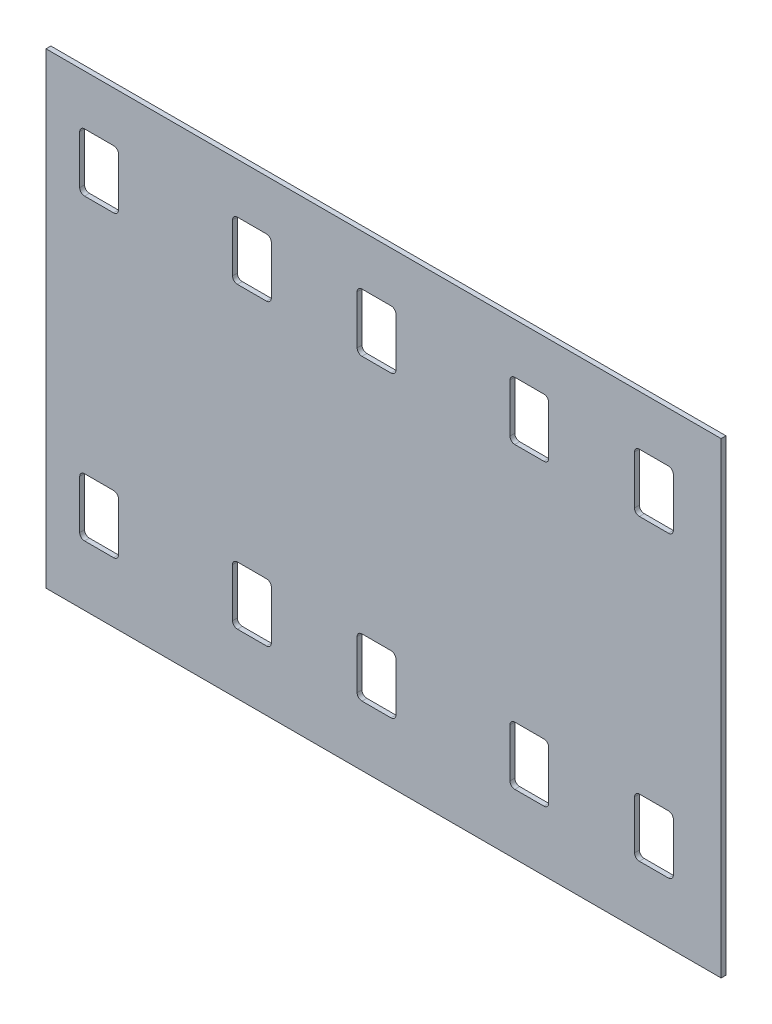
SolidWorks part; units mm, degrees
material "PP Film"
ref_plane "X-Y Datum" through (0, 0, 0) normal (0, 0, 1) x (1, 0, 0)
ref_plane "X-Z Datum" through (0, 0, 0) normal (0, 1, 0) x (1, 0, 0)
ref_plane "Y-Z Datum" through (0, 0, 0) normal (1, 0, 0) x (0, 0, -1)
sketch "Sketch1" plane through (0, 0, 0) normal (0, 0, 1) x (1, 0, 0)
  line L48 (-220.9897, 149.5877) -> (-220.9897, -156.2291)
  line L49 (-220.9897, -156.2291) -> (220.9897, -156.2291)
  line L50 (220.9897, -156.2291) -> (220.9897, 149.5877)
  line L51 (220.9897, 149.5877) -> (-220.9897, 149.5877)
extrude "Boss-Extrude1" add sketch "Sketch1" along normal blind 3.175 contours L50 L51 L48 L49 region at (0, -3.3207, 0)
sketch "Sketch2" plane through (0, 0, 3.175) normal (0, 0, 1) x (1, 0, 0)
  line L0 (-195.7605, 116.8) -> (-176.7105, 116.8) construction
  line L1 (-198.9355, 113.625) -> (-198.9355, 81.875) construction
  line L2 (-195.7605, 78.7) -> (-176.7105, 78.7) construction
  line L3 (-173.5355, 113.625) -> (-173.5355, 81.875) construction
  line L8 (-195.7605, 116.8) -> (-176.7105, 116.8)
  line L9 (-198.9355, 113.625) -> (-198.9355, 81.875)
  line L10 (-195.7605, 78.7) -> (-176.7105, 78.7)
  line L11 (-173.5355, 113.625) -> (-173.5355, 81.875)
  line L16 (-195.7605, -78.7) -> (-176.7105, -78.7) construction
  line L17 (-173.5355, -81.875) -> (-173.5355, -113.625) construction
  line L18 (-198.9355, -81.875) -> (-198.9355, -113.625) construction
  line L19 (-195.7605, -116.8) -> (-176.7105, -116.8) construction
  line L24 (-195.7605, -78.7) -> (-176.7105, -78.7)
  line L25 (-173.5355, -81.875) -> (-173.5355, -113.625)
  line L26 (-198.9355, -81.875) -> (-198.9355, -113.625)
  line L27 (-195.7605, -116.8) -> (-176.7105, -116.8)
  line L32 (-76.6655, -78.7) -> (-95.7155, -78.7) construction
  line L33 (-98.8905, -81.875) -> (-98.8905, -113.625) construction
  line L34 (-73.4905, -113.625) -> (-73.4905, -81.875) construction
  line L35 (-95.7155, -116.8) -> (-76.6655, -116.8) construction
  line L36 (-76.6655, -78.7) -> (-95.7155, -78.7)
  line L37 (-98.8905, -81.875) -> (-98.8905, -113.625)
  line L38 (-73.4905, -113.625) -> (-73.4905, -81.875)
  line L39 (-95.7155, -116.8) -> (-76.6655, -116.8)
  line L40 (-76.6655, 116.8) -> (-95.7155, 116.8) construction
  line L41 (-73.4905, 81.875) -> (-73.4905, 113.625) construction
  line L42 (-98.8905, 113.625) -> (-98.8905, 81.875) construction
  line L43 (-95.7155, 78.7) -> (-76.6655, 78.7) construction
  line L44 (-76.6655, 116.8) -> (-95.7155, 116.8)
  line L45 (-73.4905, 81.875) -> (-73.4905, 113.625)
  line L46 (-98.8905, 113.625) -> (-98.8905, 81.875)
  line L47 (-95.7155, 78.7) -> (-76.6655, 78.7)
  arc A0 (-173.5355, 113.625) -> (-176.7105, 116.8) centre (-176.7105, 113.625) ccw construction
  arc A1 (-195.7605, 116.8) -> (-198.9355, 113.625) centre (-195.7605, 113.625) ccw construction
  arc A2 (-198.9355, 81.875) -> (-195.7605, 78.7) centre (-195.7605, 81.875) ccw construction
  arc A3 (-176.7105, 78.7) -> (-173.5355, 81.875) centre (-176.7105, 81.875) ccw construction
  arc A8 (-173.5355, 113.625) -> (-176.7105, 116.8) centre (-176.7105, 113.625) ccw
  arc A9 (-195.7605, 116.8) -> (-198.9355, 113.625) centre (-195.7605, 113.625) ccw
  arc A10 (-198.9355, 81.875) -> (-195.7605, 78.7) centre (-195.7605, 81.875) ccw
  arc A11 (-176.7105, 78.7) -> (-173.5355, 81.875) centre (-176.7105, 81.875) ccw
  arc A16 (-195.7605, -78.7) -> (-198.9355, -81.875) centre (-195.7605, -81.875) ccw construction
  arc A17 (-173.5355, -81.875) -> (-176.7105, -78.7) centre (-176.7105, -81.875) ccw construction
  arc A18 (-176.7105, -116.8) -> (-173.5355, -113.625) centre (-176.7105, -113.625) ccw construction
  arc A19 (-198.9355, -113.625) -> (-195.7605, -116.8) centre (-195.7605, -113.625) ccw construction
  arc A24 (-195.7605, -78.7) -> (-198.9355, -81.875) centre (-195.7605, -81.875) ccw
  arc A25 (-173.5355, -81.875) -> (-176.7105, -78.7) centre (-176.7105, -81.875) ccw
  arc A26 (-176.7105, -116.8) -> (-173.5355, -113.625) centre (-176.7105, -113.625) ccw
  arc A27 (-198.9355, -113.625) -> (-195.7605, -116.8) centre (-195.7605, -113.625) ccw
  arc A32 (-73.4905, -81.875) -> (-76.6655, -78.7) centre (-76.6655, -81.875) ccw construction
  arc A33 (-95.7155, -78.7) -> (-98.8905, -81.875) centre (-95.7155, -81.875) ccw construction
  arc A34 (-76.6655, -116.8) -> (-73.4905, -113.625) centre (-76.6655, -113.625) ccw construction
  arc A35 (-98.8905, -113.625) -> (-95.7155, -116.8) centre (-95.7155, -113.625) ccw construction
  arc A36 (-73.4905, -81.875) -> (-76.6655, -78.7) centre (-76.6655, -81.875) ccw
  arc A37 (-95.7155, -78.7) -> (-98.8905, -81.875) centre (-95.7155, -81.875) ccw
  arc A38 (-76.6655, -116.8) -> (-73.4905, -113.625) centre (-76.6655, -113.625) ccw
  arc A39 (-98.8905, -113.625) -> (-95.7155, -116.8) centre (-95.7155, -113.625) ccw
  arc A40 (-73.4905, 113.625) -> (-76.6655, 116.8) centre (-76.6655, 113.625) ccw construction
  arc A41 (-95.7155, 116.8) -> (-98.8905, 113.625) centre (-95.7155, 113.625) ccw construction
  arc A42 (-76.6655, 78.7) -> (-73.4905, 81.875) centre (-76.6655, 81.875) ccw construction
  arc A43 (-98.8905, 81.875) -> (-95.7155, 78.7) centre (-95.7155, 81.875) ccw construction
  arc A44 (-73.4905, 113.625) -> (-76.6655, 116.8) centre (-76.6655, 113.625) ccw
  arc A45 (-95.7155, 116.8) -> (-98.8905, 113.625) centre (-95.7155, 113.625) ccw
  arc A46 (-76.6655, 78.7) -> (-73.4905, 81.875) centre (-76.6655, 81.875) ccw
  arc A47 (-98.8905, 81.875) -> (-95.7155, 78.7) centre (-95.7155, 81.875) ccw
extrude "Cut-Extrude1" cut sketch "Sketch2" against normal through all contours L26 A27 L27 A26 L25 A25 L24 A24 | L10 A11 L11 A8 L8 A9 L9 A10 region at (-186.2355, 97.75, 3.175) region at (-186.2355, -97.75, 3.175)
sketch "Sketch3" plane through (0, 0, 3.175) normal (0, 0, 1) x (1, 0, 0)
  line L5 (-176.7105, 116.8) -> (-195.7605, 116.8)
  line L6 (-173.5355, 81.875) -> (-173.5355, 113.625)
  line L7 (-195.7605, 78.7) -> (-176.7105, 78.7)
  line L13 (-198.9355, 113.625) -> (-198.9355, 81.875)
  line L14 (-176.7105, 116.8) -> (-195.7605, 116.8)
  line L15 (-173.5355, 81.875) -> (-173.5355, 113.625)
  line L21 (-195.7605, 78.7) -> (-176.7105, 78.7)
  line L22 (-198.9355, 113.625) -> (-198.9355, 81.875)
  line L23 (-173.5355, -113.625) -> (-173.5355, -81.875)
  line L29 (-195.7605, -116.8) -> (-176.7105, -116.8)
  line L30 (-198.9355, -81.875) -> (-198.9355, -113.625)
  line L31 (-176.7105, -78.7) -> (-195.7605, -78.7)
  line L36 (-173.5355, -113.625) -> (-173.5355, -81.875)
  line L37 (-195.7605, -116.8) -> (-176.7105, -116.8)
  line L38 (-198.9355, -81.875) -> (-198.9355, -113.625)
  line L39 (-176.7105, -78.7) -> (-195.7605, -78.7)
  line L40 (-76.6655, 116.8) -> (-95.7155, 116.8)
  line L41 (-98.8905, 113.625) -> (-98.8905, 81.875)
  line L42 (-95.7155, 78.7) -> (-76.6655, 78.7)
  line L43 (-73.4905, 81.875) -> (-73.4905, 113.625)
  line L44 (-76.6655, 116.8) -> (-95.7155, 116.8)
  line L45 (-98.8905, 113.625) -> (-98.8905, 81.875)
  line L46 (-95.7155, 78.7) -> (-76.6655, 78.7)
  line L47 (-73.4905, 81.875) -> (-73.4905, 113.625)
  line L48 (-95.7155, -116.8) -> (-76.6655, -116.8)
  line L49 (-98.8905, -81.875) -> (-98.8905, -113.625)
  line L50 (-76.6655, -78.7) -> (-95.7155, -78.7)
  line L51 (-73.4905, -113.625) -> (-73.4905, -81.875)
  line L52 (-95.7155, -116.8) -> (-76.6655, -116.8)
  line L53 (-98.8905, -81.875) -> (-98.8905, -113.625)
  line L54 (-76.6655, -78.7) -> (-95.7155, -78.7)
  line L55 (-73.4905, -113.625) -> (-73.4905, -81.875)
  arc A36 (-173.5355, 113.625) -> (-176.7105, 116.8) centre (-176.7105, 113.625) ccw
  arc A37 (-176.7105, 78.7) -> (-173.5355, 81.875) centre (-176.7105, 81.875) ccw
  arc A38 (-198.9355, 81.875) -> (-195.7605, 78.7) centre (-195.7605, 81.875) ccw
  arc A39 (-195.7605, 116.8) -> (-198.9355, 113.625) centre (-195.7605, 113.625) ccw
  arc A40 (-173.5355, 113.625) -> (-176.7105, 116.8) centre (-176.7105, 113.625) ccw
  arc A41 (-176.7105, 78.7) -> (-173.5355, 81.875) centre (-176.7105, 81.875) ccw
  arc A42 (-198.9355, 81.875) -> (-195.7605, 78.7) centre (-195.7605, 81.875) ccw
  arc A43 (-195.7605, 116.8) -> (-198.9355, 113.625) centre (-195.7605, 113.625) ccw
  arc A44 (-176.7105, -116.8) -> (-173.5355, -113.625) centre (-176.7105, -113.625) ccw
  arc A45 (-198.9355, -113.625) -> (-195.7605, -116.8) centre (-195.7605, -113.625) ccw
  arc A46 (-195.7605, -78.7) -> (-198.9355, -81.875) centre (-195.7605, -81.875) ccw
  arc A47 (-173.5355, -81.875) -> (-176.7105, -78.7) centre (-176.7105, -81.875) ccw
  arc A48 (-176.7105, -116.8) -> (-173.5355, -113.625) centre (-176.7105, -113.625) ccw
  arc A49 (-198.9355, -113.625) -> (-195.7605, -116.8) centre (-195.7605, -113.625) ccw
  arc A50 (-195.7605, -78.7) -> (-198.9355, -81.875) centre (-195.7605, -81.875) ccw
  arc A51 (-173.5355, -81.875) -> (-176.7105, -78.7) centre (-176.7105, -81.875) ccw
  arc A52 (-95.7155, 116.8) -> (-98.8905, 113.625) centre (-95.7155, 113.625) ccw
  arc A53 (-98.8905, 81.875) -> (-95.7155, 78.7) centre (-95.7155, 81.875) ccw
  arc A54 (-76.6655, 78.7) -> (-73.4905, 81.875) centre (-76.6655, 81.875) ccw
  arc A55 (-73.4905, 113.625) -> (-76.6655, 116.8) centre (-76.6655, 113.625) ccw
  arc A56 (-95.7155, 116.8) -> (-98.8905, 113.625) centre (-95.7155, 113.625) ccw
  arc A57 (-98.8905, 81.875) -> (-95.7155, 78.7) centre (-95.7155, 81.875) ccw
  arc A58 (-76.6655, 78.7) -> (-73.4905, 81.875) centre (-76.6655, 81.875) ccw
  arc A59 (-73.4905, 113.625) -> (-76.6655, 116.8) centre (-76.6655, 113.625) ccw
  arc A60 (-76.6655, -116.8) -> (-73.4905, -113.625) centre (-76.6655, -113.625) ccw
  arc A61 (-98.8905, -113.625) -> (-95.7155, -116.8) centre (-95.7155, -113.625) ccw
  arc A62 (-95.7155, -78.7) -> (-98.8905, -81.875) centre (-95.7155, -81.875) ccw
  arc A63 (-73.4905, -81.875) -> (-76.6655, -78.7) centre (-76.6655, -81.875) ccw
  arc A64 (-76.6655, -116.8) -> (-73.4905, -113.625) centre (-76.6655, -113.625) ccw
  arc A65 (-98.8905, -113.625) -> (-95.7155, -116.8) centre (-95.7155, -113.625) ccw
  arc A66 (-95.7155, -78.7) -> (-98.8905, -81.875) centre (-95.7155, -81.875) ccw
  arc A67 (-73.4905, -81.875) -> (-76.6655, -78.7) centre (-76.6655, -81.875) ccw
  dimension "D1" = 0
  dimension "D2" = 0
  dimension "D3" = 0
  dimension "D4" = 0
extrude "Cut-Extrude2" cut sketch "Sketch3" against normal through all contours L55 A67 L54 A66 L53 A65 L52 A64 | L47 A59 L44 A56 L45 A57 L46 A58 region at (-86.1905, 97.75, 3.175) region at (-86.1905, -97.75, 3.175)
pattern_linear "LPattern1" count 3 spacing 181.614 along (1, 0, 0) of "Cut-Extrude1"
pattern_linear "LPattern2" count 2 spacing 181.614 along (1, 0, 0) of "Cut-Extrude2"
